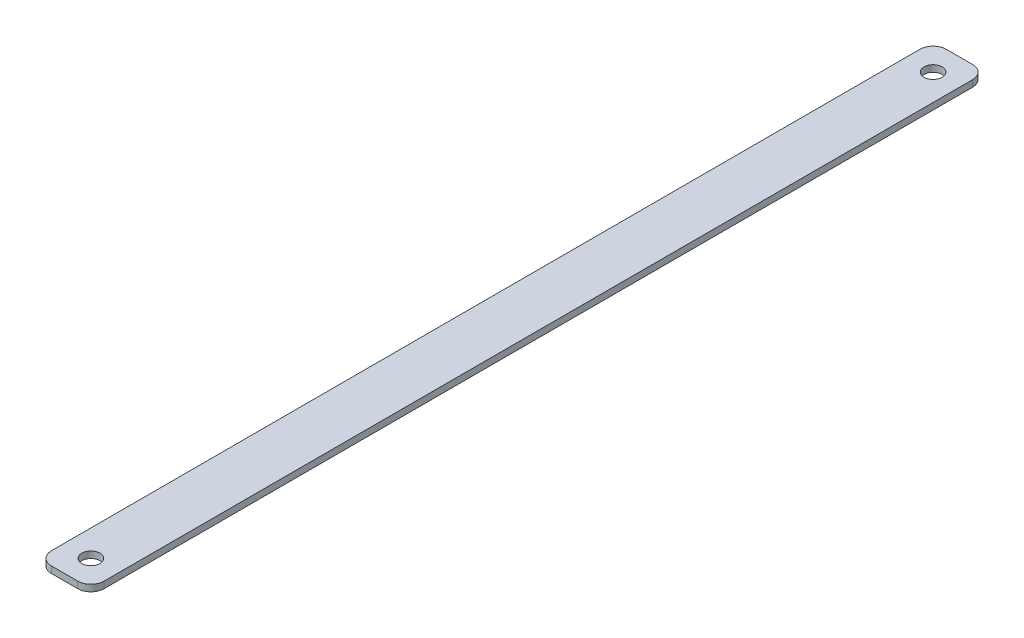
SolidWorks part; units mm, degrees
ref_plane "Front Plane" through (0, 0, 0) normal (0, 0, 1) x (1, 0, 0)
ref_plane "Top Plane" through (0, 0, 0) normal (0, 1, 0) x (1, 0, 0)
ref_plane "Right Plane" through (0, 0, 0) normal (1, 0, 0) x (0, 0, -1)
sketch "Sketch1" plane through (0, 0, 0) normal (0, 1, 0) x (1, 0, 0)
  line L1 (3.175, 0) -> (9.525, 0)
  line L2 (0, 3.175) -> (0, 212.725)
  line L3 (3.175, 215.9) -> (9.525, 215.9)
  line L4 (12.7, 3.175) -> (12.7, 212.725)
  circle A0 centre (6.35, 209.55) radius 2.1828
  arc A1 (3.175, 215.9) -> (0, 212.725) centre (3.175, 212.725) ccw
  arc A2 (12.7, 212.725) -> (9.525, 215.9) centre (9.525, 212.725) ccw
  arc A3 (3.175, 0) -> (0, 3.175) centre (3.175, 3.175) cw
  arc A4 (12.7, 3.175) -> (9.525, 0) centre (9.525, 3.175) cw
  circle A5 centre (6.35, 6.35) radius 2.1828
  point P13 (0, 0)
  dimension "D5" = 4.3656
  dimension "D6" = 3.175
  dimension "D7" = 3.175
  dimension "D8" = 3.175
  dimension "D9" = 3.175
  dimension "D12" = 4.3656
  dimension "D1" = 12.7
  dimension "D2" = 215.9
  dimension "D3" = 6.35
  dimension "D4" = 6.35
  dimension "D10" = 6.35
  dimension "D11" = 6.35
extrude "Boss-Extrude1" add sketch "Sketch1" along normal mid plane 1.5875
